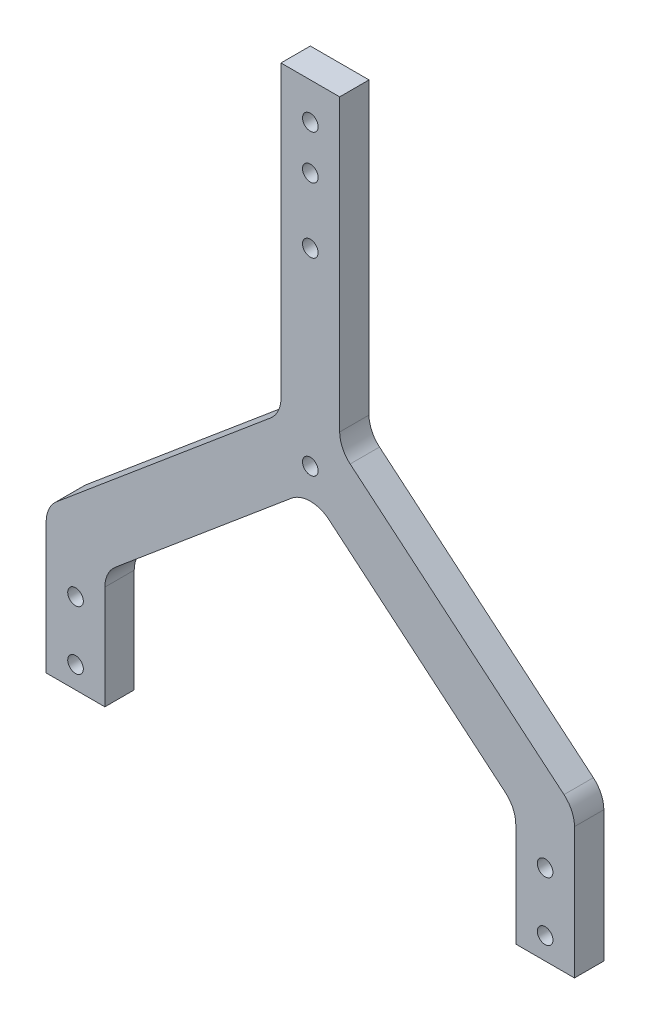
SolidWorks part; units mm, degrees
ref_plane "Front Plane" through (0, 0, 0) normal (0, 0, 1) x (1, 0, 0)
ref_plane "Top Plane" through (0, 0, 0) normal (0, 1, 0) x (1, 0, 0)
ref_plane "Right Plane" through (0, 0, 0) normal (1, 0, 0) x (0, 0, -1)
sketch "Sketch1" plane through (0, 0, 0) normal (0, 0, 1) x (1, 0, 0)
  line L0 (-88.9, 0) -> (88.9, 0) construction
  line L1 (-88.9, 0) -> (-114.3, 0)
  line L2 (-114.3, 0) -> (-114.3, 62.6442)
  line L3 (-88.9, 0) -> (-88.9, 50.8)
  line L4 (-88.9, 50.8) -> (-25.4, 104.0828)
  line L5 (-88.9, 50.8) -> (-114.3, 62.6442) construction
  line L6 (-114.3, 62.6442) -> (-41.7268, 123.5404)
  line L7 (-41.7268, 123.5404) -> (-12.7, 147.8967)
  line L8 (-25.4, 104.0828) -> (0, 125.396)
  line L9 (0, 125.396) -> (0, 278.1608) construction
  line L10 (-25.4, 104.0828) -> (-41.7268, 123.5404) construction
  line L11 (-12.7, 147.8967) -> (-12.7, 279.4)
  line L12 (-12.7, 279.4) -> (12.7, 279.4)
  line L13 (25.4, 104.0828) -> (41.7268, 123.5404) construction
  line L14 (88.9, 50.8) -> (114.3, 62.6442) construction
  line L15 (12.7, 147.8967) -> (12.7, 279.4)
  line L16 (25.4, 104.0828) -> (0, 125.396)
  line L17 (41.7268, 123.5404) -> (12.7, 147.8967)
  line L18 (114.3, 62.6442) -> (41.7268, 123.5404)
  line L19 (88.9, 50.8) -> (25.4, 104.0828)
  line L20 (88.9, 0) -> (88.9, 50.8)
  line L21 (114.3, 0) -> (114.3, 62.6442)
  line L22 (88.9, 0) -> (114.3, 0)
  point P2 (0, 0)
  point P19 (0, 279.4)
  dimension "D1" = 177.8
  dimension "D2" = 115
  dimension "D3" = 115
  dimension "D4" = 50.8
  dimension "D5" = 25.4
  dimension "D6" = 90
  dimension "D7" = 90
  dimension "D8" = 25.4
  dimension "D9" = 12.7
  dimension "D10" = 279.4
extrude "Boss-Extrude1" add sketch "Sketch1" along normal mid plane 12.7
fillet "Fillet1" radius 12.7 7 edges at (-12.7, 147.8967, 0) (12.7, 147.8967, 0) (-114.3, 62.6442, 0) (114.3, 62.6442, 0) (88.9, 50.8, 0) (0, 125.396, 0) (-88.9, 50.8, 0)
hole_wizard "1/4 Clearance Hole1" positions "Sketch2" profile "Sketch3" hole size "1/4" standard "ANSI Inch" end condition through all
sketch "Sketch2" plane through (0, 0, 6.35) normal (0, 0, 1) x (1, 0, 0)
  line L0 (-101.6, 0) -> (-101.6, 73.3008) construction
  line L1 (-114.3, 0) -> (-88.9, 0) construction
  line L2 (-17.2366, 144.0901) -> (-109.7634, 66.4509) construction
  line L4 (101.6, 0) -> (101.6, 73.3008) construction
  line L5 (88.9, 0) -> (114.3, 0) construction
  line L6 (109.7634, 66.4509) -> (17.2366, 144.0901) construction
  line L7 (-101.6, 9.525) -> (101.6, 9.525) construction
  line L9 (-101.6, 34.925) -> (101.6, 34.925) construction
  point P16 (-101.6, 9.525)
  point P18 (-101.6, 34.925)
  point P22 (101.6, 9.525)
  point P26 (101.6, 34.925)
  dimension "D1" = 9.525
  dimension "D2" = 25.4
sketch "Sketch3" plane through (101.6, 34.925, 6.35) normal (1, 0, 0) x (0, -1, 0)
  line L0 (0, 0) -> (0, 12.7)
  line L1 (0, 12.7) -> (3.3782, 12.7)
  line L2 (3.3782, 12.7) -> (3.3782, 0)
  line L5 (3.3782, 0) -> (0, 0)
  line L11 (0, -6.35) -> (0, 107.95) construction
  dimension "Thru Hole Dia." = 6.7564
  dimension "Thru Hole Depth" = 12.7
hole_wizard "1/4 Clearance Hole2" positions "Sketch4" profile "Sketch5" hole size "1/4" standard "ANSI Inch" end condition through all
sketch "Sketch4" plane through (0, 0, 6.35) normal (0, 0, 1) x (1, 0, 0)
  line L0 (0, 279.4) -> (0, 244.475) construction
  line L1 (12.7, 279.4) -> (-12.7, 279.4) construction
  point P1 (0, 244.475)
  point P9 (0, 263.525)
  dimension "D1" = 34.925
  dimension "D2" = 19.05
sketch "Sketch5" plane through (0, 263.525, 6.35) normal (1, 0, 0) x (0, -1, 0)
  line L0 (0, 0) -> (0, 12.7)
  line L1 (0, 12.7) -> (3.3782, 12.7)
  line L2 (3.3782, 12.7) -> (3.3782, 0)
  line L5 (3.3782, 0) -> (0, 0)
  line L11 (0, -6.35) -> (0, 107.95) construction
  dimension "Thru Hole Dia." = 6.7564
  dimension "Thru Hole Depth" = 12.7
hole_wizard "1/4 Clearance Hole3" positions "Sketch6" profile "Sketch8" hole size "1/4" standard "ANSI Inch" end condition through all
sketch "Sketch6" plane through (0, 0, -6.35) normal (0, 0, -1) x (-1, 0, 0)
  circle A0 centre (0, 134.62) radius 2.5527 construction
  circle A1 centre (0, 134.62) radius 2.5527
  point P1 (0, 134.62)
sketch "Sketch8" plane through (0, 134.62, -6.35) normal (1, 0, 0) x (0, 1, 0)
  line L0 (0, 0) -> (0, 12.7)
  line L1 (0, 12.7) -> (3.3782, 12.7)
  line L2 (3.3782, 12.7) -> (3.3782, 0)
  line L5 (3.3782, 0) -> (0, 0)
  line L11 (0, -6.35) -> (0, 107.95) construction
  dimension "Thru Hole Dia." = 6.7564
  dimension "Thru Hole Depth" = 12.7
hole_wizard "1/4 Clearance Hole4" positions "Sketch9" profile "Sketch10" hole size "1/4" standard "ANSI Inch" end condition through all
sketch "Sketch9" plane through (0, 0, 6.35) normal (0, 0, 1) x (1, 0, 0)
  point P0 (0, 216.3194)
sketch "Sketch10" plane through (0, 216.3194, 6.35) normal (1, 0, 0) x (0, -1, 0)
  line L0 (0, 0) -> (0, 12.7)
  line L1 (0, 12.7) -> (3.3782, 12.7)
  line L2 (3.3782, 12.7) -> (3.3782, 0)
  line L5 (3.3782, 0) -> (0, 0)
  line L11 (0, -6.35) -> (0, 107.95) construction
  dimension "Thru Hole Dia." = 6.7564
  dimension "Thru Hole Depth" = 12.7
equation "\"D3@Sketch1\"=\"D2@Sketch1\""
equation "\"D7@Sketch1\"=\"D6@Sketch1\""
